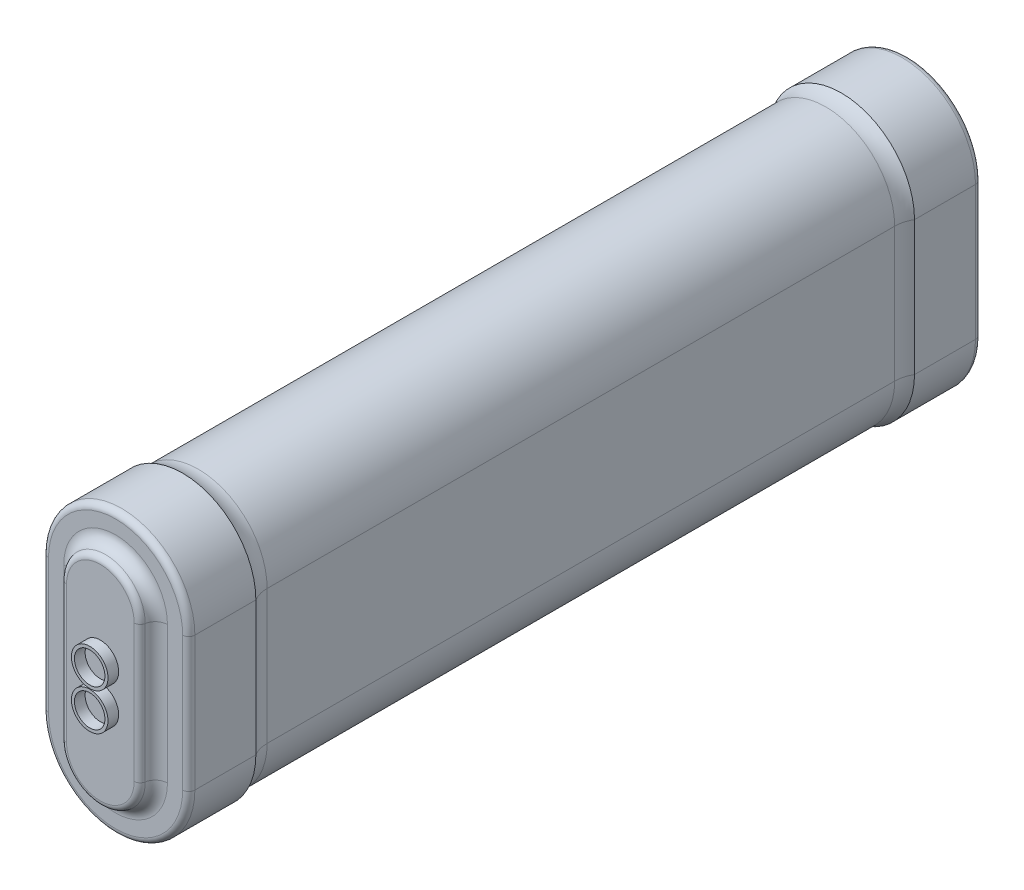
SolidWorks part; units mm, degrees
material "PVC 0.007 Plasticized"
ref_plane "Front Plane" through (0, 0, 0) normal (0, 0, 1) x (1, 0, 0)
ref_plane "Top Plane" through (0, 0, 0) normal (0, 1, 0) x (1, 0, 0)
ref_plane "Right Plane" through (0, 0, 0) normal (1, 0, 0) x (0, 0, -1)
sketch "Sketch1" plane through (0, 0, 0) normal (0, 0, 1) x (1, 0, 0)
  line L0 (-12, -11) -> (-12, 11)
  line L1 (12, 11) -> (12, -11)
  line L2 (-12, 0) -> (12, 0) construction
  arc A0 (-12, 11) -> (12, 11) centre (0, 11) cw
  arc A1 (12, -11) -> (-12, -11) centre (0, -11) cw
  point P6 (-12, 0)
  point P7 (12, 0)
  point P10 (0, 0)
  dimension "D2" = 12
  dimension "D1" = 22
ref_plane "Plane1" through (0, 0, 0) normal (0, 0, 1) x (1, 0, 0)
extrude "Boss-Extrude2" add sketch "Sketch1" along normal mid plane 130
sketch "Sketch2" plane through (0, 0, 0) normal (0, 0, 1) x (1, 0, 0)
  line L0 (0, 11) -> (0, -11) construction
  line L1 (-11.3, 11) -> (-11.3, -11)
  line L2 (11.3, -11) -> (11.3, 11)
  line L3 (15, 11) -> (15, -11)
  line L4 (-15, -11) -> (-15, 11)
  arc A0 (-11.3, -11) -> (11.3, -11) centre (0, -11) ccw
  arc A1 (11.3, 11) -> (-11.3, 11) centre (0, 11) ccw
  arc A2 (-15, 11) -> (15, 11) centre (0, 11) cw
  arc A3 (15, -11) -> (-15, -11) centre (0, -11) cw
  dimension "D2" = 11.3
  dimension "D3" = 15
  dimension "D1" = 22
  dimension "D4" = 22
extrude "Cut-Extrude1" cut sketch "Sketch2" against normal mid plane 108
fillet "Fillet1" radius 5 8 edges at (0, -22.3, 54) (11.3, 0, 54) (0, 22.3, 54) (-11.3, 0, 54) (-11.3, 0, -54) (0, -22.3, -54) (11.3, 0, -54) (0, 22.3, -54)
fillet "Fillet2" radius 1 8 edges at (0, -23, -65) (12, 0, -65) (0, 23, -65) (-12, 0, -65) (-12, 0, 65) (0, -23, 65) (12, 0, 65) (0, 23, 65)
sketch "Sketch3" plane through (0, 0, 65) normal (0, 0, 1) x (1, 0, 0)
  line L0 (0, 11.25) -> (0, -11.25) construction
  line L1 (-6.5, -11.25) -> (-6.5, 11.25)
  line L2 (6.5, 11.25) -> (6.5, -11.25)
  arc A0 (6.5, -11.25) -> (-6.5, -11.25) centre (0, -11.25) cw
  arc A1 (-6.5, 11.25) -> (6.5, 11.25) centre (0, 11.25) cw
  dimension "D2" = 6.5
  dimension "D1" = 22.5
extrude "Boss-Extrude3" add sketch "Sketch3" along normal blind 2.5
fillet "Fillet4" radius 2 4 edges at (-6.5, 0, 65) (0, -17.75, 65) (0, 17.75, 65) (6.5, 0, 65)
fillet "Fillet5" radius 1 4 edges at (-6.5, 0, 67.5) (0, 17.75, 67.5) (6.5, 0, 67.5) (0, -17.75, 67.5)
sketch "Sketch4" plane through (0, 0, 67.5) normal (0, 0, 1) x (1, 0, 0)
  line L0 (0, 3.05) -> (0, -3.05) construction
  circle A0 centre (0, 3.05) radius 3
  circle A1 centre (0, -3.05) radius 3
  circle A2 centre (0, 3.05) radius 2.5
  circle A3 centre (0, -3.05) radius 2.5
  point P7 (-0.7681, -0.15)
  dimension "D1" = 6
  dimension "D3" = 5
  dimension "D2" = 6.1
extrude "Boss-Extrude8" add sketch "Sketch4" along normal blind 1.75
